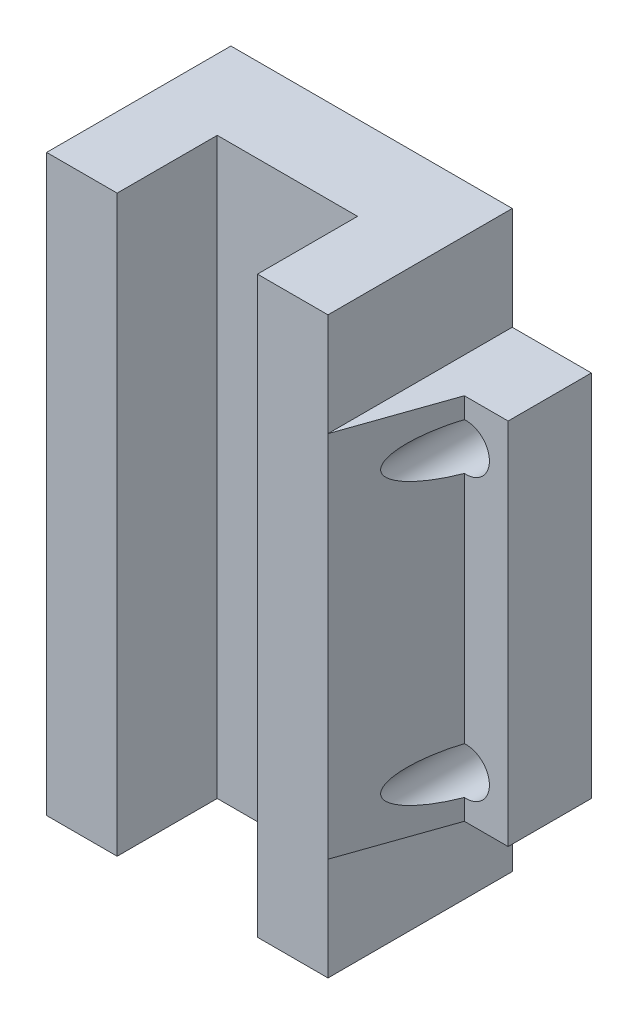
SolidWorks part; units mm, degrees
ref_plane "前视基准面" through (0, 0, 0) normal (0, 0, 1) x (1, 0, 0)
ref_plane "上视基准面" through (0, 0, 0) normal (0, 1, 0) x (1, 0, 0)
ref_plane "右视基准面" through (0, 0, 0) normal (1, 0, 0) x (0, 0, -1)
other "Configuration Table"
sketch "草图5" plane through (0, 0, 0) normal (0, 1, 0) x (1, 0, 0)
  line L1 (23.5, -9.85) -> (-23.5, -9.85)
  line L2 (23.5, -9.85) -> (23.5, 9.85)
  line L3 (23.5, 9.85) -> (-23.5, 9.85)
  line L4 (-23.5, -9.85) -> (-23.5, 9.85)
  line L5 (23.5, -9.85) -> (-23.5, 9.85) construction
  line L6 (23.5, 9.85) -> (-23.5, -9.85) construction
  point P0 (0, 0)
  dimension "D1" = 47
  dimension "D2" = 19.7
extrude "凸台-拉伸3" add sketch "草图5" along normal blind 61.4
sketch "草图6" plane through (0, 61.4, 0) normal (0, 1, 0) x (1, 0, 0)
  line L0 (-23.5, 9.85) -> (-23.5, 0.95)
  line L1 (-23.5, 9.85) -> (-23.5, -9.85) construction
  line L2 (-23.5, 0.95) -> (-18.8195, 0.95)
  line L3 (-18.8195, 0.95) -> (-15.0407, -9.85)
  line L4 (-23.5, -9.85) -> (23.5, -9.85) construction
  line L5 (-19, 9.85) -> (-19, 6.7564)
  line L6 (23.5, 9.85) -> (-23.5, 9.85) construction
  line L7 (0, 9.85) -> (0, -9.85)
  line L8 (23.5, 9.85) -> (23.5, -9.85)
  line L9 (19, 9.85) -> (19, 6.7564)
  line L10 (18.8195, 0.95) -> (15.0407, -9.85)
  line L11 (23.5, 0.95) -> (18.8195, 0.95)
  line L12 (-23.5, 9.85) -> (-23.5, -9.85)
  line L13 (-23.5, -9.85) -> (23.5, -9.85)
  line L14 (23.5, -9.85) -> (23.5, 9.85)
  line L15 (23.5, 9.85) -> (-23.5, 9.85)
  line L16 (-23.5, 9.85) -> (-23.5, -9.85)
  line L17 (-23.5, -9.85) -> (23.5, -9.85)
  line L18 (23.5, -9.85) -> (23.5, 9.85)
  line L19 (23.5, 9.85) -> (-23.5, 9.85)
  line L20 (23.5, 9.85) -> (23.5, 0.95)
  line L22 (-15.0407, -9.85) -> (15.0407, -9.85)
  line L23 (-15.0407, -9.85) -> (-15.0407, 9.85)
  line L24 (-15.0407, 9.85) -> (15.0407, 9.85)
  line L25 (15.0407, -9.85) -> (15.0407, 9.85)
  line M1 (-23.5, 9.85) -> (-23.5, -9.85)
  line M2 (-23.5, -9.85) -> (23.5, -9.85)
  line M3 (23.5, -9.85) -> (23.5, 9.85)
  line M4 (23.5, 9.85) -> (-23.5, 9.85)
  dimension "D1" = 8.9
  dimension "D2" = 19
  dimension "D3" = 0
extrude "切除-拉伸1" cut sketch "草图6" against normal through all contours L3 L2 M1 M2 | L11 L10 M3 M2 region at (-20.1245, 61.4, 4.9677) region at (20.1245, 61.4, 4.9677)
extrude "切除-拉伸2" cut sketch "草图6<6>" against normal blind 11 contours L3 L23 L19 L2 M4 M1 | L25 L10 L11 L8 M4 region at (-18.637, 61.4, -3.6834) region at (18.637, 61.4, -3.6834)
sketch "草图6<6>" plane through (0, 61.4, 0) normal (0, 1, 0) x (1, 0, 0) same geometry as "草图6"
ref_plane "基准面1" through (0, 30.7, 0) normal (0, 1, 0) x (1, 0, 0)
mirror "镜向1" about plane through (0, 30.7, 0) normal (0, 1, 0) of "切除-拉伸2"
sketch "草图8" plane through (0, 0, -9.85) normal (0, 0, -1) x (-1, 0, 0)
  line L0 (-23.5, 50.4) -> (-15.0407, 50.4) construction
  line L2 (-23.5, 11) -> (-15.0407, 11) construction
  line L3 (0, 61.4) -> (0, 0)
  line L4 (-15.0407, 61.4) -> (15.0407, 61.4) construction
  circle A0 centre (-19, 45.7) radius 2.5
  circle A1 centre (-19, 15.7) radius 2.5
  circle A2 centre (19, 15.7) radius 2.5
  circle A3 centre (19, 45.7) radius 2.5
  point P4 (-19, 14.8783)
  point P12 (-19, 15.4)
  point P15 (-19, 45.7)
  point P20 (0, 0)
  dimension "D1" = 5
  dimension "D3" = 5
  dimension "D2" = 19
  dimension "D4" = 30
  dimension "D5" = 4.7
  dimension "D6" = 4.7
extrude "切除-拉伸3" cut sketch "草图8" against normal blind 33 contours A1 | A2 | A3 | A0 region at (19, 15.7, -9.85) region at (-19, 15.7, -9.85) region at (-19, 45.7, -9.85)
sketch "草图9" plane through (0, 0, 0) normal (0, -1, 0) x (1, 0, 0)
  line L0 (-15.0407, 9.85) -> (15.0407, 9.85) construction
  line L1 (7.5, -0.85) -> (-7.5, -0.85)
  line L2 (7.5, -0.85) -> (7.5, 21.1316)
  line L3 (7.5, 21.1316) -> (-7.5, 21.1316)
  line L4 (-7.5, -0.85) -> (-7.5, 21.1316)
  line L5 (7.5, -0.85) -> (-7.5, 21.1316) construction
  line L6 (7.5, 21.1316) -> (-7.5, -0.85) construction
  point P0 (0, 10.1408)
  point P5 (0, 11.2757)
  point P6 (0, 11.3275)
  dimension "D1" = 15
  dimension "D2" = 10.7
extrude "切除-拉伸4" cut sketch "草图9" against normal blind 73
